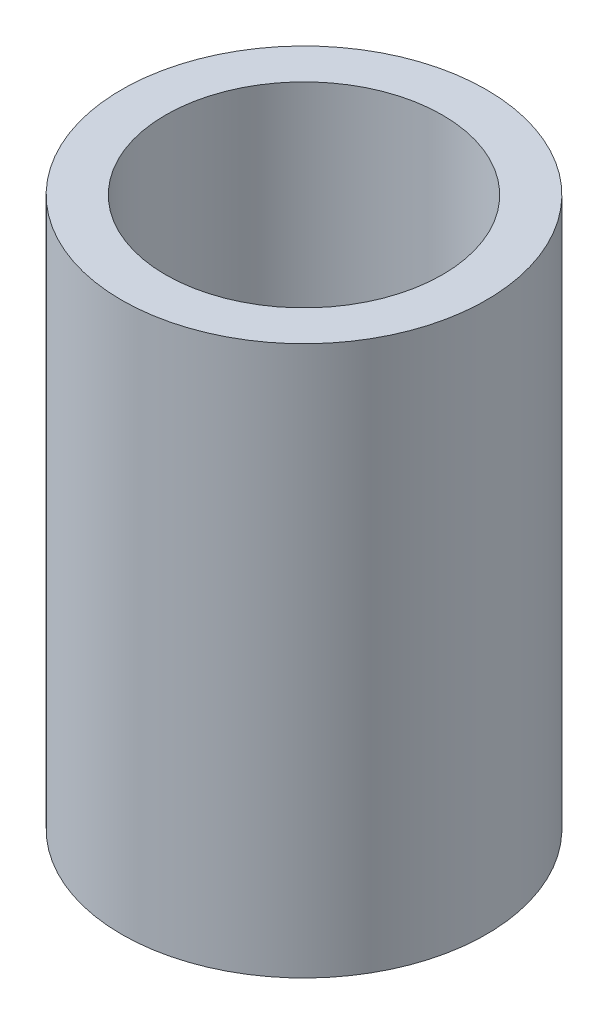
SolidWorks part; units mm, degrees
ref_plane "Front Plane" through (0, 0, 0) normal (0, 0, 1) x (1, 0, 0)
ref_plane "Top Plane" through (0, 0, 0) normal (0, 1, 0) x (1, 0, 0)
ref_plane "Right Plane" through (0, 0, 0) normal (1, 0, 0) x (0, 0, -1)
sketch "Sketch1" plane through (0, 0, 0) normal (0, 1, 0) x (1, 0, 0)
  circle A0 centre (0, 0) radius 4
  circle A1 centre (0, 0) radius 5.27
  dimension "D1" = 8
  dimension "D2" = 1.27
extrude "Boss-Extrude1" add sketch "Sketch1" along normal blind 15.875
